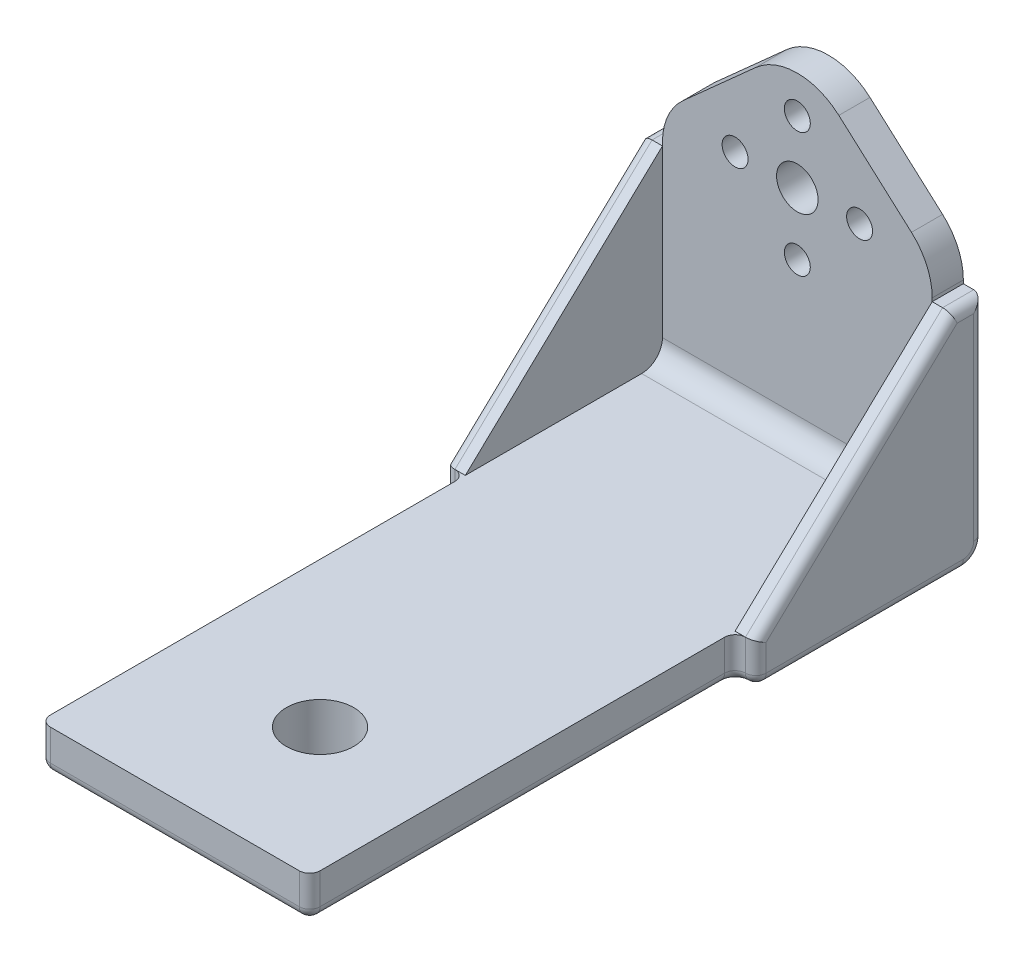
SolidWorks part; units mm, degrees
ref_plane "Front Plane" through (0, 0, 0) normal (0, 0, 1) x (1, 0, 0)
ref_plane "Top Plane" through (0, 0, 0) normal (0, 1, 0) x (1, 0, 0)
ref_plane "Right Plane" through (0, 0, 0) normal (1, 0, 0) x (0, 0, -1)
sketch "Sketch1" plane through (0, 0, 0) normal (0, 0, 1) x (1, 0, 0)
  line L0 (0, 11.4628) -> (0, -12.0557) construction
  line L1 (-13.1568, 0) -> (14.2861, 0) construction
  line L2 (-13, -2.6826) -> (-13, -25)
  line L3 (-11.0009, 1.7888) -> (-4.0009, 8.0523)
  line L4 (13, -2.6826) -> (13, -25)
  line L5 (11.0009, 1.7888) -> (4.0009, 8.0523)
  line L6 (-13, -25) -> (13, -25)
  circle A0 centre (0, 0) radius 2
  circle A1 centre (-6, 0) radius 1.25
  circle A2 centre (0, 6) radius 1.25
  circle A3 centre (6, 0) radius 1.25
  circle A4 centre (0, -6) radius 1.25
  arc A5 (13, -2.6826) -> (11.0009, 1.7888) centre (7, -2.6826) ccw
  arc A6 (4.0009, 8.0523) -> (-4.0009, 8.0523) centre (0, 3.5809) ccw
  arc A7 (-13, -2.6826) -> (-11.0009, 1.7888) centre (-7, -2.6826) cw
  point P18 (0, 0)
  point P23 (13, 0)
  point P26 (0, 11.6322)
  point P29 (-13, 0)
  dimension "D1" = 4
  dimension "D2" = 2.5
  dimension "D6" = 6
  dimension "D3" = 6
  dimension "D5" = 26
  dimension "D7" = 25
  dimension "D4" = 4
extrude "Boss-Extrude1" add sketch "Sketch1" along normal blind 3
sketch "Sketch2" plane through (0, 0, 3) normal (0, 0, 1) x (1, 0, 0)
  line L0 (13, -25) -> (13, -2.6826) construction
  line L1 (-13, -25) -> (13, -25)
  line L2 (-13, -25) -> (-13, -21)
  line L3 (-13, -21) -> (13, -21)
  line L4 (13, -25) -> (13, -21)
  dimension "D1" = 4
extrude "Boss-Extrude2" add sketch "Sketch2" along normal blind 60
sketch "Sketch3" plane through (0, -21, 0) normal (0, 1, 0) x (1, 0, 0)
  line L0 (13, -63) -> (13, -3) construction
  line L2 (13, -3) -> (-13, -3) construction
  circle A0 centre (1, -50) radius 3.25
  dimension "D1" = 6.5
  dimension "D2" = 12
  dimension "D3" = 47
extrude "Cut-Extrude1" cut sketch "Sketch3" against normal through all
sketch "Sketch4" plane through (0, -25, 0) normal (0, -1, 0) x (1, 0, 0)
  line L4 (-13, 0) -> (13, 0)
  line L5 (13, 0) -> (13, 63)
  line L6 (13, 63) -> (-13, 63)
  line L7 (-13, 63) -> (-13, 0)
  line L8 (-13, 0) -> (13, 0)
  line L9 (13, 0) -> (13, 63)
  line L10 (13, 63) -> (-13, 63)
  line L11 (-13, 63) -> (-13, 0)
  circle A0 centre (1, 50) radius 3.25 construction
  circle A1 centre (1, 50) radius 3.25
  circle A2 centre (1, 50) radius 8
  circle M6 centre (1, 50) radius 3.25
  dimension "D2" = 16
  dimension "D1" = 0
extrude "Boss-Extrude3" add sketch "Sketch4" along normal blind 1 contours A2 M6
sketch "Sketch5" plane through (0, -25, 0) normal (0, -1, 0) x (1, 0, 0)
  line L0 (-13, 10) -> (13, 10) construction
  line L1 (-13, 63) -> (-13, 0) construction
  line L2 (13, 63) -> (13, 0) construction
  line L3 (-13, 0) -> (13, 0) construction
  line L4 (0, 16.476) -> (0, 4.5805) construction
  circle A0 centre (-7.5, 10) radius 1.5
  circle A1 centre (7.5, 10) radius 1.5
  dimension "D2" = 3
  dimension "D1" = 10
  dimension "D3" = 15
extrude "Boss-Extrude4" add sketch "Sketch5" along normal blind 3
sketch "Sketch6" plane through (-13, 0, 0) normal (-1, 0, 0) x (0, 0, 1)
  line L0 (0, -3) -> (3, -3)
  line L1 (0, -2.6826) -> (0, -25) construction
  line L2 (3, -2.6826) -> (3, -21) construction
  line L3 (3, -3) -> (22, -21)
  line L4 (63, -21) -> (3, -21) construction
  line L5 (22, -21) -> (22, -25)
  line L6 (63, -25) -> (0, -25) construction
  line L7 (22, -25) -> (0, -25)
  line L8 (0, -25) -> (0, -3)
  dimension "D1" = 22
  dimension "D2" = 22
extrude "Boss-Extrude5" add sketch "Sketch6" along normal blind 2
mirror "Mirror1" about plane through (0, 0, 0) normal (1, 0, 0) of "Boss-Extrude5"
fillet "Fillet1" radius 2 2 edges at (0, -25, 0) (0, -21, 3)
fillet "Fillet2" radius 1 21 edges at (13, -23, 22) (15, -13, 0) (15, -3, 1.5) (15, -12, 12.5) (15, -23, 22) (14, -25, 22) (15, -25, 12) (-15, -25, 12) (15, -24.4142, 0.5858) (-15, -24.4142, 0.5858) (-13, -25, 42.5) (13, -25, 42.5) (-13, -23, 63) (0, -25, 63) (13, -23, 63) (-13, -23, 22) (-14, -25, 22) (-15, -13, 0) (-15, -23, 22) (-15, -12, 12.5) (-15, -3, 1.5)
fillet "Fillet3" radius 0.5 2 edges at (6, -28, 10) (-6, -28, 10)
